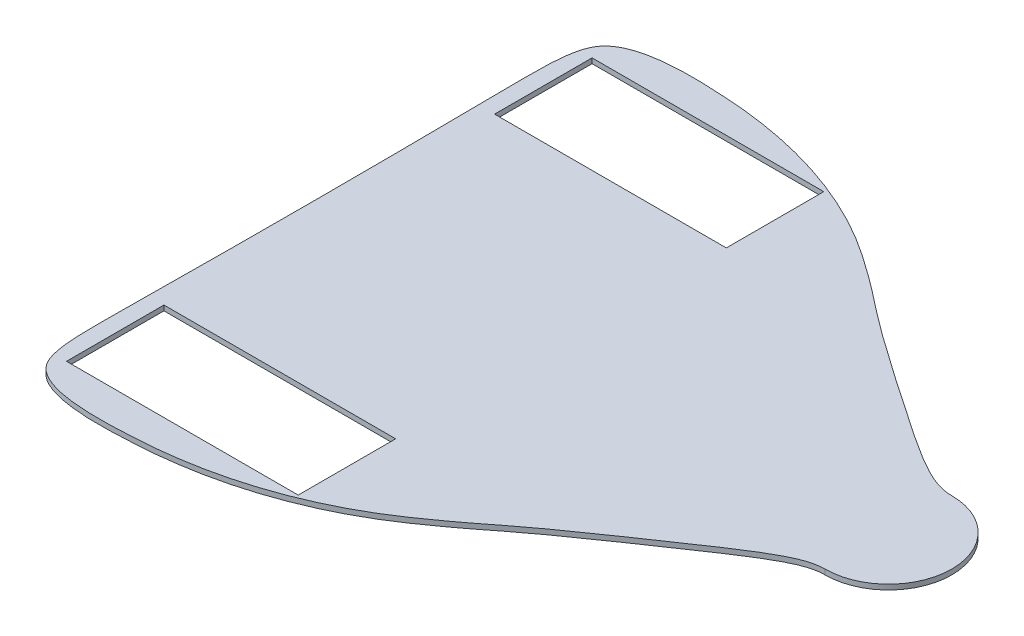
SolidWorks part; units mm, degrees
material "PLA"
ref_plane "Front Plane" through (0, 0, 0) normal (0, 0, 1) x (1, 0, 0)
ref_plane "Top Plane" through (0, 0, 0) normal (0, 1, 0) x (1, 0, 0)
ref_plane "Right Plane" through (0, 0, 0) normal (1, 0, 0) x (0, 0, -1)
sketch "base dimensions" plane through (0, 0, 0) normal (0, 1, 0) x (1, 0, 0)
  line L0 (0, 0) -> (-116.6267, 0) construction
  line L2 (-112.85, 41.1) -> (-112.85, -41.1)
  line L3 (-96.85, 41.1) -> (-96.85, -41.1)
  line L5 (-112.85, 41.1) -> (-96.85, -41.1) construction
  line L6 (-96.85, 41.1) -> (-112.85, -41.1) construction
  line L7 (-131.85, -27.5) -> (-114.85, -27.5)
  line L8 (-131.85, -27.5) -> (-131.85, 27.5)
  line L9 (-114.85, -27.5) -> (-114.85, 27.5)
  line L10 (-131.85, 27.5) -> (-114.85, 27.5)
  line L11 (-131.85, -27.5) -> (-114.85, 27.5) construction
  line L12 (-114.85, -27.5) -> (-131.85, 27.5) construction
  line L13 (-94.85, 0) -> (-94.85, 10.9056)
  line L14 (-135.85, -577.028) -> (-135.85, 577.028) construction
  line L16 (-130.25, -60.15) -> (-79.45, -60.15)
  line L17 (-130.25, 41.1) -> (-79.45, 41.1)
  line L18 (-130.25, 41.1) -> (-130.25, 60.15)
  line L19 (-130.25, 60.15) -> (-79.45, 60.15)
  line L20 (-79.45, 41.1) -> (-79.45, 60.15)
  line L21 (-79.45, -41.1) -> (-79.45, -60.15)
  line L22 (-130.25, -41.1) -> (-79.45, -41.1)
  line L23 (-130.25, -41.1) -> (-130.25, -60.15)
  circle A0 centre (0, 0) radius 63.5 construction
  circle A1 centre (0, 0) radius 15
  circle A2 centre (-81, 0) radius 13.85
  spline S0 degree 3 poles (0, 15) (-4.8701, 15) (-11.57, 19.2171) (-47.1414, 43.6327) (-47.2901, 44.7578) (-76.416, 65.5552) (-102.1519, 69.4095) (-110.5415, 69.8488) (-132.3896, 71.7277) (-136.9471, 56.9085) (-135.85, 46.8022) (-135.85, 0) knots 0 0 0 0 0.067079 0.083664 0.156713 0.181875 0.310125 0.366504 0.689288 0.756673 1 1 1 1
  spline S1 degree 3 poles (0, -15) (-4.8701, -15) (-11.57, -19.2171) (-47.1414, -43.6327) (-47.2901, -44.7578) (-76.416, -65.5552) (-102.1519, -69.4095) (-110.5415, -69.8488) (-132.3896, -71.7277) (-136.9471, -56.9085) (-135.85, -46.8022) (-135.85, 0) knots 0 0 0 0 0.067079 0.083664 0.156713 0.181875 0.310125 0.366504 0.689288 0.756673 1 1 1 1
  point P4 (-96.85, 0)
  point P8 (-67.15, 0)
  point P10 (-104.85, 0)
  point P11 (-63.5, 0)
  point P20 (-123.35, 0)
  point P27 (-114.85, 0)
  point P34 (-225.1572, 0)
  point P36 (0, 0)
  point P38 (0, 0)
  point P40 (-182.9144, 0)
  point P41 (0, 0)
  point P42 (0, 0)
  point P44 (-183.9048, 41.0069)
  point P45 (-70.6005, 86.3682)
  point P46 (-44.2553, 53.4862)
  point P47 (-129.2335, 101.4226)
  point P48 (-152.2113, 0)
  point P49 (-157.7576, 53.2881)
  point P50 (-150.8247, 88.15)
  point P51 (-110.0193, 101.4226)
  point P52 (-140.966, 97.0647)
  point P53 (-151.0228, 64.1827)
  point P54 (-148.8438, 0)
  point P55 (-148.8438, 65.3713)
  point P56 (-52.3768, 53.8824)
  point P62 (-152.2331, 0)
  point P63 (-148.7532, 0)
  point P66 (-141.9496, 93.9747)
  point P67 (-147.5409, 0)
  point P68 (-149.2087, 69.1)
  point P69 (-139.5726, 94.4346)
  point P70 (0, 0)
  point P71 (-147.4021, 69.1)
  point P72 (-147.9536, 53.9726)
  point P73 (-132.3279, 98.2759)
  point P74 (-135.8207, 97.3568)
  point P75 (-91.501, 93.864)
  point P76 (0, 0)
  point P77 (0, 0)
  point P78 (0, 0)
  point P79 (-45.3255, 30.2742)
  point P80 (-68.3036, 56.9402)
  point P81 (-146.2566, 0)
  point P82 (-67.15, 97.771)
  point P83 (-127.2816, 69.1)
  point P84 (-173.6205, 69.1)
  point P85 (-127.6167, 94.8989)
  point P86 (0, 0)
  point P87 (-130.25, 69.1)
  point P88 (-125.0845, 100.3676)
  point P89 (-70.157, 88.15)
  point P90 (-127.0819, 94.3755)
  point P91 (-71.1557, 83.1903)
  point P92 (-51.5815, 46.8382)
  point P93 (-49.9836, 53.03)
  point P94 (-125.4984, 94.2733)
  point P95 (0, 0)
  point P96 (0, 0)
  point P97 (0, 0)
  point P98 (0, 0)
  point P99 (0, 0)
  point P100 (0, 0)
  point P101 (-131.85, 27.5)
  point P102 (-75.1324, 88.15)
  point P103 (-129.1907, 98.7386)
  point P104 (-71.4794, 88.15)
  point P105 (-125.9501, 99.5511)
  point P106 (-126.4679, 98.8262)
  point P107 (-78.0022, 68.2812)
  point P108 (-125.2012, 79.1894)
  point P109 (-135.85, 55)
  point P110 (-135.85, 55)
  point P111 (-127.4509, 63.8903)
  point P112 (-69.5802, 52.2594)
  point P113 (-104.85, 71.5497)
  point P114 (-28.1246, 30.5849)
  point P115 (-63.5, 47.9159)
  point P116 (-104.85, 65.2941)
  point P117 (-59.1091, 50.1088)
  point P118 (-135.85, 58.1833)
  point P119 (-104.85, 68.2671)
  point P120 (-57.1832, 51.7935)
  point P121 (-135.85, 60.15)
  point P122 (-135.85, 57.2599)
  point P123 (-134.0364, 60.15)
  point P124 (-135.0328, 62.8723)
  point P125 (-102.6752, 68.6068)
  point P126 (-103.4719, 69.4035)
  dimension "D1" = 127
  dimension "D2" = 30
  dimension "D5" = 27.7
  dimension "D9" = 2
  dimension "D10" = 81
  dimension "D15" = 90
  dimension "D3" = 82.2
  dimension "D4" = 16
  dimension "D6" = 55
  dimension "D7" = 17
  dimension "D8" = 2
  dimension "D11" = 19.05
  dimension "D12" = 50.8
  dimension "D14" = 3.65
  dimension "D18" = 4
extrude "Boss-Extrude1" add sketch "base dimensions" against normal blind 1.2 contours S1 A1 S0 L23 L22 L2 L17 L18 L19 L20 L3 L21 L16 A2 L8 L10 L9 L7 | L22 L23 L16 L21 | L2 L22 L3 L17 | L10 L8 L7 L9 | L17 L20 L19 L18 | A2 | A1 region at (-104.85, 0, 0) region at (-104.85, 0, -50.625) region at (-104.85, 0, 50.625) region at (-123.35, 0, 0) region at (0, 0, 0) region at (-16.9542, 0, 0) region at (-81, 0, 0)
sketch "Sketch2" plane through (0, -1.2, 0) normal (0, -1, 0) x (-1, 0, 0)
  line L4 (-200000, 0) -> (200116.6267, 0) construction
  line L5 (-200000, 0) -> (200116.6267, 0)
  line L8 (132.25, 39.1) -> (132.25, 62.15)
  line L9 (77.45, 39.1) -> (132.25, 39.1)
  line L10 (77.45, 62.15) -> (77.45, 39.1)
  line L11 (132.25, 62.15) -> (77.45, 62.15)
  line L12 (132.25, 39.1) -> (132.25, 62.15)
  line L13 (77.45, 39.1) -> (132.25, 39.1)
  line L14 (77.45, 62.15) -> (77.45, 39.1)
  line L15 (132.25, 62.15) -> (77.45, 62.15)
  line L22 (77.45, -62.15) -> (132.25, -62.15)
  line L23 (77.45, -39.1) -> (77.45, -62.15)
  line L24 (132.25, -39.1) -> (77.45, -39.1)
  line L25 (132.25, -62.15) -> (132.25, -39.1)
  line L26 (77.45, -62.15) -> (132.25, -62.15)
  line L27 (77.45, -39.1) -> (77.45, -62.15)
  line L28 (132.25, -39.1) -> (77.45, -39.1)
  line L29 (132.25, -62.15) -> (132.25, -39.1)
  point P2 (-132.25, -67.1)
  point P4 (0, 0)
  point P5 (0, 0)
  dimension "D1" = 2
  dimension "D2" = 2
extrude "Cut-Extrude1" cut sketch "Sketch2" against normal through all
